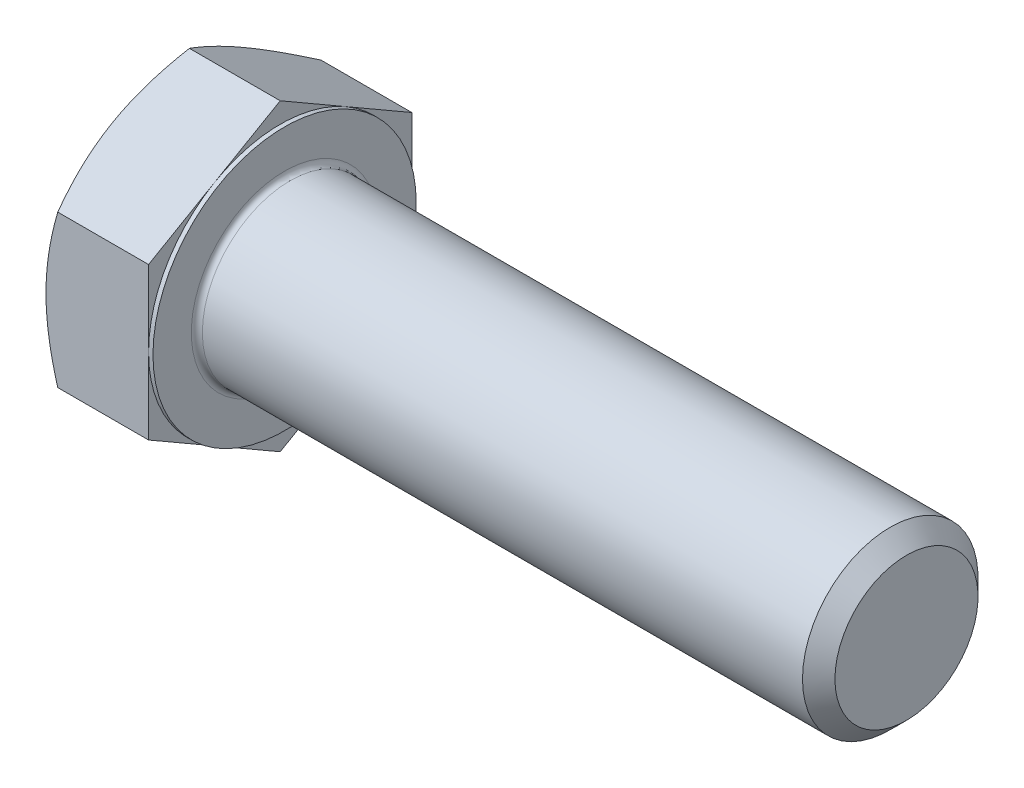
SolidWorks part; units mm, degrees
ref_plane "Front Plane" through (0, 0, 0) normal (0, 0, 1) x (1, 0, 0)
ref_plane "Top Plane" through (0, 0, 0) normal (0, 1, 0) x (1, 0, 0)
ref_plane "Right Plane" through (0, 0, 0) normal (1, 0, 0) x (0, 0, -1)
sketch "BaseHeadSke" plane through (0, 0, 0) normal (1, 0, 0) x (0, 0, -1)
  line L1 (19.05, 10.9985) -> (0, 21.997)
  line L2 (0, 21.997) -> (-19.05, 10.9985)
  line L3 (-19.05, 10.9985) -> (-19.05, -10.9985)
  line L4 (-19.05, -10.9985) -> (0, -21.997)
  line L5 (0, -21.997) -> (19.05, -10.9985)
  line L6 (19.05, -10.9985) -> (19.05, 10.9985)
  circle A0 centre (0, 0) radius 19.05 construction
extrude "BaseHead" add sketch "BaseHeadSke" along normal blind 15.4781
sketch "BodySke" plane through (0, 0, 0) normal (0, 0, 1) x (1, 0, 0)
  line L0 (0, 0) -> (105.4781, 0)
  line L1 (105.4781, 0) -> (105.4781, 10.352)
  line L2 (105.4781, 10.352) -> (103.1301, 12.7)
  line L3 (103.1301, 12.7) -> (0, 12.7)
  line L4 (0, 12.7) -> (0, 0)
  line L5 (15.4781, 10.9985) -> (15.4781, -10.9985) construction
  line L6 (0, 0) -> (159.3976, 0) construction
  line L7 (51.4781, -84.3176) -> (51.4781, 77.7215) construction
  line L8 (102.4781, -21.5941) -> (102.4781, 39.2994) construction
  dimension "Thread_length" = 54
  dimension "Advance" = 3
revolve "BaseBody" add sketch "BodySke" angle 360 about L6
cosmetic thread "ThreadCosmetic" [suppressed] parameters "Thread_length"=54, "Thread_minor"=20.704
sketch "HeadChamferSke" plane through (0, 0, 0) normal (0, 0, 1) x (1, 0, 0)
  line L0 (1.7015, 21.997) -> (0, 21.997)
  line L1 (0, 21.997) -> (0, 19.05)
  line L2 (0, 19.05) -> (1.7015, 21.997)
  line L3 (0, 0) -> (120.9185, 0) construction
  dimension "D1" = 30
revolve "HeadChamfer" cut sketch "HeadChamferSke" angle 360 about L3
sketch "BearingFaceSke" plane through (0, 0, 0) normal (0, 0, 1) x (1, 0, 0)
  line L0 (0, 0) -> (129.6443, 0) construction
  line L1 (14.8431, 21.997) -> (15.4781, 21.997)
  line L2 (14.8431, 21.997) -> (14.8431, 19.05)
  line L3 (14.8431, 19.05) -> (15.4781, 19.05)
  line L4 (15.4781, 21.997) -> (15.4781, 19.05)
revolve "BearingFace" cut sketch "BearingFaceSke" angle 360 about L0
fillet "Fillet" radius 0.8 1 edges at (15.4781, 0, -12.7)
sketch "ThdSchSke" plane through (0, 0, 0) normal (0, 0, 1) x (1, 0, 0)
  line L0 (101.1225, 15.4112) -> (101.1225, 12.7)
  line L1 (101.1225, 12.7) -> (102.4781, 10.352)
  line L2 (102.4781, 10.352) -> (103.8337, 12.7)
  line L3 (103.8337, 12.7) -> (103.8337, 15.4112)
  line L4 (103.8337, 15.4112) -> (101.1225, 15.4112)
  line L6 (0, 0) -> (141.9934, 0) construction
  line L7 (105.4781, -10.352) -> (105.4781, 10.352) construction
  dimension "D2" = 20.704
  dimension "D3" = 25.4
  dimension "Advance" = 3
revolve "ThreadSchematic" [suppressed] cut sketch "ThdSchSke" angle 360 about L6
pattern_linear "ThdSchPat" [suppressed] count 17 spacing 3 along (-1, 0, 0) of bodies 107
equation "\"Thread_minor@ThreadCosmetic\" = \"Minor_dia@BodySke\""
equation "\"Thread_length@ThreadCosmetic\" = \"Thread_length@BodySke\""
equation "\"Head_chamfer@HeadChamferSke\" = \"Width_flats@BaseHeadSke\""
equation "\"D2@ThdSchSke\" = \"Minor_dia@BodySke\""
equation "\"D3@ThdSchSke\" = \"Diameter@BodySke\""
equation "\"Advance@ThdSchSke\" = \"Advance@BodySke\""
equation "\"D3@ThdSchPat\" = \"Advance@BodySke\""
equation "\"D1@ThdSchPat\" =  int( \"Thread_length@BodySke\"/\"Advance@BodySke\" )-1"
equation "\"Dw@BearingFaceSke\"=\"Width_flats@BaseHeadSke\""
